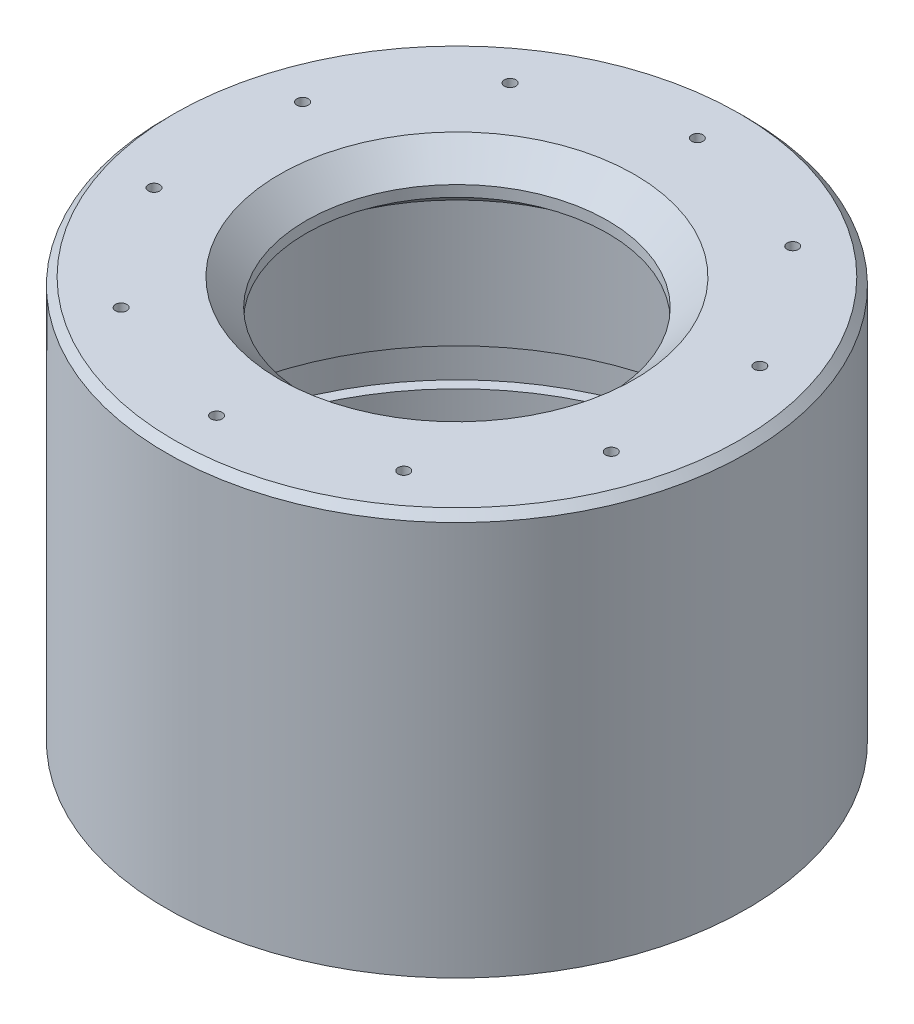
SolidWorks part; units mm, degrees
ref_plane "정면" through (0, 0, 0) normal (0, 0, 1) x (1, 0, 0)
ref_plane "윗면" through (0, 0, 0) normal (0, 1, 0) x (1, 0, 0)
ref_plane "우측면" through (0, 0, 0) normal (1, 0, 0) x (0, 0, -1)
sketch "스케치1" plane through (0, 0, 0) normal (0, 0, 1) x (1, 0, 0)
  line L0 (58.2341, 90.172) -> (58.2341, 100.048) construction
  line L1 (18.2341, 96.6) -> (16.3121, 96.6)
  line L2 (11.163, 106.6) -> (-18.75, 106.6)
  line L3 (-18.75, 106.6) -> (-18.75, 101.6949)
  line L4 (-13.75, 96.6) -> (-13.75, 39.8655)
  line L5 (-13.75, 39.8655) -> (-16.6611, 39.8655)
  line L6 (-16.6611, 39.8655) -> (-16.6611, 30)
  line L7 (-16.6611, 30) -> (-13.75, 30)
  line L8 (-13.75, 30) -> (-13.75, 0)
  line L9 (-13.75, 0) -> (-18.75, 0)
  line L10 (-18.75, 0) -> (-18.75, 101.6949)
  line L12 (3.2341, 96.6) -> (3.2341, 88.6)
  line L13 (3.2341, 88.6) -> (7.7962, 88.6)
  line L14 (7.7962, 88.6) -> (16.3121, 96.6)
  line L15 (3.2341, 96.6) -> (-13.75, 96.6)
  line L16 (18.2341, 99.5289) -> (18.2341, 96.6)
  line L17 (11.163, 106.6) -> (18.2341, 99.5289)
  point P2 (3.2341, 96.6)
  point P17 (11.3064, 106.6)
  dimension "D1" = 10
  dimension "D2" = 135
  dimension "D3" = 10
  dimension "D4" = 96.6
  dimension "D5" = 30
  dimension "D6" = 55
  dimension "D7" = 8
  dimension "D8" = 40
revolve "회전1" add sketch "스케치1" angle 360 about L0
sketch "스케치2" plane through (0, 96.6, 0) normal (0, -1, 0) x (1, 0, 0)
  line L0 (58.2341, 63.75) -> (58.2341, 0) construction
  circle A0 centre (58.2341, 0) radius 63.75 construction
  circle A5 centre (58.2341, 63.75) radius 1.5
  circle A6 centre (58.2341, 63.75) radius 3
  dimension "D1" = 127.5
extrude "컷-돌출1" cut sketch "스케치2" against normal through all contours A5
extrude "컷-돌출2" cut sketch "스케치2<3>" against normal blind 3
sketch "스케치2<3>" plane through (0, 96.6, 0) normal (0, -1, 0) x (1, 0, 0) same geometry as "스케치2"
ref_axis "기준축1" through (58.2341, 106.6, 0) along (0, -1, 0)
pattern_circular "원형 패턴1" count 10 over 360 about axis through (58.2341, 106.6, 0) along (0, -1, 0) of "컷-돌출1", "컷-돌출2"
chamfer "모따기1" distance 2 angle 45 1 edges at (58.2341, 106.6, -76.9841)
